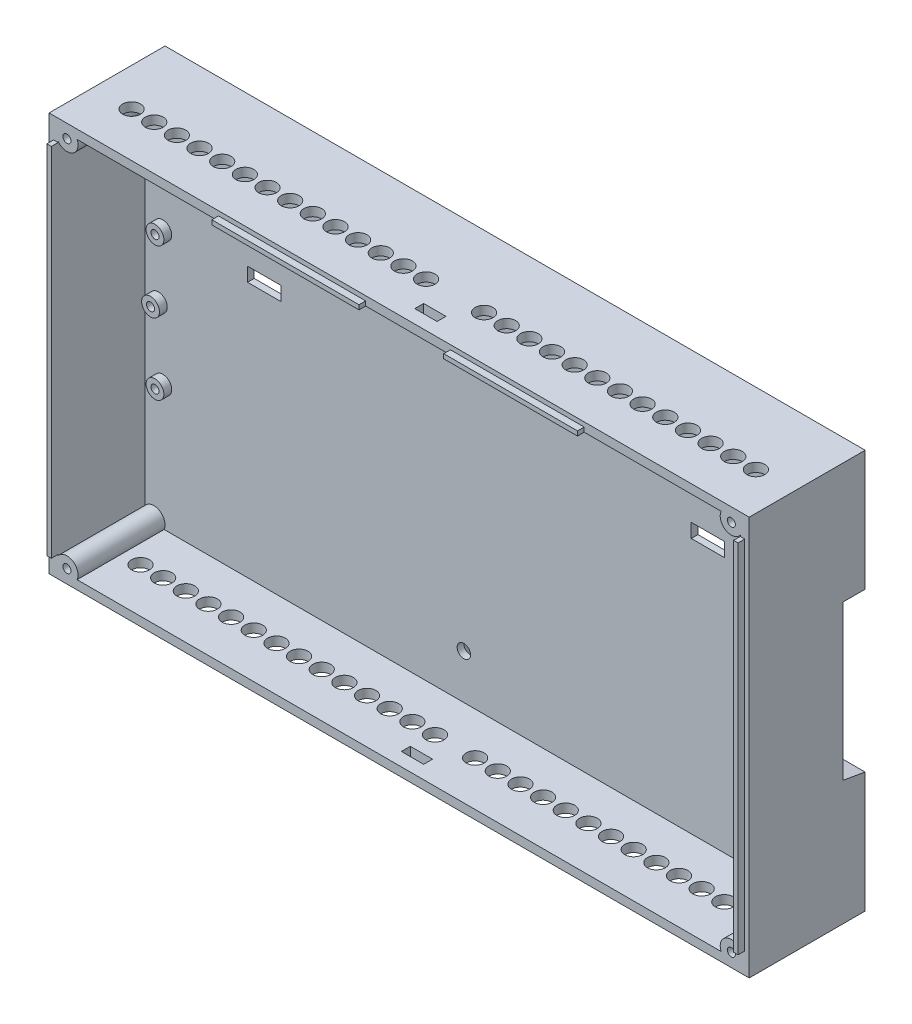
SolidWorks part; units mm, degrees
ref_plane "Front Plane" through (0, 0, 0) normal (0, 0, 1) x (1, 0, 0)
ref_plane "Top Plane" through (0, 0, 0) normal (0, 1, 0) x (1, 0, 0)
ref_plane "Right Plane" through (0, 0, 0) normal (1, 0, 0) x (0, 0, -1)
sketch "Sketch1" plane through (0, 0, 0) normal (0, 0, 1) x (1, 0, 0)
  line L1 (-78.5, 44.75) -> (78.5, 44.75)
  line L2 (-78.5, 44.75) -> (-78.5, -44.75)
  line L3 (-78.5, -44.75) -> (78.5, -44.75)
  line L4 (78.5, 44.75) -> (78.5, -44.75)
  line L5 (-78.5, 44.75) -> (78.5, -44.75) construction
  line L6 (-78.5, -44.75) -> (78.5, 44.75) construction
  point P0 (0, 0)
  dimension "D1" = 157
  dimension "D2" = 89.5
extrude "Boss-Extrude1" add sketch "Sketch1" along normal blind 26
sketch "Sketch2" plane through (0, 0, 26) normal (0, 0, 1) x (1, 0, 0)
  line L0 (78.5, 44.75) -> (-78.5, 44.75) construction
  line L1 (-76.5, 42.75) -> (76.5, 42.75)
  line L2 (-76.5, 42.75) -> (-76.5, -42.75)
  line L3 (-76.5, -42.75) -> (76.5, -42.75)
  line L4 (76.5, 42.75) -> (76.5, -42.75)
  line L5 (-76.5, 42.75) -> (76.5, -42.75) construction
  line L6 (-76.5, -42.75) -> (76.5, 42.75) construction
  line L7 (-78.5, 44.75) -> (-78.5, -44.75) construction
  point P0 (0, 0)
  dimension "D1" = 2
  dimension "D2" = 2
extrude "Cut-Extrude1" cut sketch "Sketch2" against normal blind 19.5
sketch "Sketch3" plane through (0, 0, 0) normal (0, 0, -1) x (-1, 0, 0)
  line L0 (-78.5, -44.75) -> (-78.5, 44.75) construction
  line L1 (-78.5, 17.75) -> (78.5, 17.75)
  line L2 (-78.5, 17.75) -> (-78.5, -17.75)
  line L3 (-78.5, -17.75) -> (78.5, -17.75)
  line L4 (78.5, 17.75) -> (78.5, -17.75)
  line L5 (78.5, 44.75) -> (78.5, -44.75) construction
  line L6 (78.5, -44.75) -> (-78.5, -44.75) construction
  line L7 (-78.5, 44.75) -> (78.5, 44.75) construction
  dimension "D1" = 27
  dimension "D2" = 27
extrude "Cut-Extrude2" cut sketch "Sketch3" against normal blind 5
sketch "Sketch4" plane through (0, 0, 0) normal (0, 0, -1) x (-1, 0, 0)
  line L0 (78.5, 44.75) -> (78.5, 17.75) construction
  line L1 (-76.5, 42.75) -> (76.5, 42.75)
  line L2 (-76.5, 42.75) -> (-76.5, 19.75)
  line L3 (-76.5, 19.75) -> (76.5, 19.75)
  line L4 (76.5, 42.75) -> (76.5, 19.75)
  line L5 (-76.5, 42.75) -> (76.5, 19.75) construction
  line L6 (-76.5, 19.75) -> (76.5, 42.75) construction
  line L7 (-78.5, 44.75) -> (78.5, 44.75) construction
  line L8 (78.5, 17.75) -> (-78.5, 17.75) construction
  line L9 (78.5, -17.75) -> (78.5, -44.75) construction
  line L10 (-76.5, -19.75) -> (76.5, -19.75)
  line L11 (-76.5, -19.75) -> (-76.5, -42.75)
  line L12 (-76.5, -42.75) -> (76.5, -42.75)
  line L13 (76.5, -19.75) -> (76.5, -42.75)
  line L14 (-76.5, -19.75) -> (76.5, -42.75) construction
  line L15 (-76.5, -42.75) -> (76.5, -19.75) construction
  line L16 (78.5, -44.75) -> (-78.5, -44.75) construction
  line L18 (-78.5, -17.75) -> (78.5, -17.75) construction
  point P0 (0, 31.25)
  point P12 (0, -31.25)
  dimension "D1" = 2
  dimension "D2" = 0
  dimension "D3" = 2
  dimension "D4" = 2
  dimension "D5" = 2
  dimension "D6" = 0
  dimension "D7" = 2
  dimension "D8" = 2
extrude "Cut-Extrude3" cut sketch "Sketch4" against normal blind 5
chamfer "Chamfer1" distance 5 angle 10 1 edges at (0, -17.75, 5) first distance on face at (0, -17.75, 2.5)
sketch "Sketch5" plane through (0, 0, 5) normal (0, 0, -1) x (-1, 0, 0)
  line L0 (76.5, -19.75) -> (-76.5, -19.75) construction
  line L1 (-8.75, -19.75) -> (8.75, -19.75)
  line L2 (-8.75, -19.75) -> (-8.75, -42.75)
  line L3 (-8.75, -42.75) -> (8.75, -42.75)
  line L4 (8.75, -19.75) -> (8.75, -42.75)
  line L5 (-76.5, -42.75) -> (76.5, -42.75) construction
  dimension "D1" = 17.5
  dimension "D2" = 8.75
extrude "Boss-Extrude2" add sketch "Sketch5" along normal up to surface (5 mm away) up to face at (0, -31.25, 0)
sketch "Sketch6" plane through (0, -44.75, 0) normal (0, -1, 0) x (1, 0, 0)
  line L0 (-78.5, 0) -> (78.5, 0) construction
  line L1 (7.25, 2) -> (-7.25, 2)
  line L2 (7.25, 2) -> (7.25, 5)
  line L3 (7.25, 5) -> (-7.25, 5)
  line L4 (-7.25, 2) -> (-7.25, 5)
  point P6 (0, 0)
  dimension "D1" = 14.5
  dimension "D2" = 7.25
  dimension "D3" = 2
  dimension "D4" = 5
extrude "Cut-Extrude4" cut sketch "Sketch6" against normal up to next
sketch "Sketch7" plane through (0, 0, 0) normal (0, 0, -1) x (-1, 0, 0)
  line L0 (78.5, -44.75) -> (-78.5, -44.75) construction
  line L1 (-6, -31.75) -> (6, -31.75)
  line L2 (-6, -31.75) -> (-6, -44.75)
  line L3 (-6, -44.75) -> (6, -44.75)
  line L4 (6, -31.75) -> (6, -44.75)
  line L5 (-6, -31.75) -> (6, -44.75) construction
  line L6 (-6, -44.75) -> (6, -31.75) construction
  point P0 (0, -38.25)
  dimension "D1" = 12
  dimension "D2" = 0
  dimension "D3" = 0
  dimension "D4" = 13
extrude "Cut-Extrude5" cut sketch "Sketch7" against normal up to next
chamfer "Chamfer2" distance 2 angle 21 1 edges at (6, -44.75, 1) first distance on face at (6, -38.25, 1)
chamfer "Chamfer3" distance 2 angle 21 1 edges at (-6, -44.75, 1) first distance on face at (-6, -38.25, 1)
sketch "Sketch8" plane through (0, 0, 5) normal (0, 0, -1) x (-1, 0, 0)
  line L0 (78.5, -17.75) -> (78.5, -44.75) construction
  line L1 (-7.25, -44.75) -> (7.25, -44.75) construction
  circle A0 centre (5, -32.75) radius 1.5
  dimension "D1" = 3
  dimension "D2" = 73.5
  dimension "D3" = 12
extrude "Cut-Extrude6" cut sketch "Sketch8" against normal through all
sketch "Sketch9" plane through (0, 17.75, 0) normal (0, -1, 0) x (1, 0, 0)
  line L0 (-78.5, 0) -> (78.5, 0) construction
  line L1 (53.5, 0) -> (46, 0)
  line L2 (53.5, 0) -> (53.5, 3)
  line L3 (53.5, 3) -> (46, 3)
  line L4 (46, 0) -> (46, 3)
  line L5 (78.5, 5) -> (78.5, 0) construction
  line L6 (0, -14.7612) -> (0, 18.2694) construction
  line L7 (-46, 0) -> (-46, 3)
  line L8 (-53.5, 3) -> (-46, 3)
  line L9 (-53.5, 0) -> (-53.5, 3)
  line L10 (-53.5, 0) -> (-46, 0)
  dimension "D1" = 7.5
  dimension "D2" = 32.5
  dimension "D3" = 3
extrude "Boss-Extrude3" add sketch "Sketch9" along normal blind 3
sketch "Sketch10" plane through (0, 0, 5) normal (0, 0, -1) x (-1, 0, 0)
  line L0 (78.5, 17.75) -> (-78.5, 17.75) construction
  line L1 (-53.5, 17.75) -> (-46, 17.75)
  line L2 (-53.5, 17.75) -> (-53.5, 14.6132)
  line L3 (-53.5, 14.6132) -> (-46, 14.6132)
  line L4 (-46, 17.75) -> (-46, 14.6132)
  line L5 (-78.5, 17.75) -> (-78.5, -16.8684) construction
  line L6 (0, -6.1265) -> (0, 10.5776) construction
  line L7 (46, 17.75) -> (46, 14.6132)
  line L8 (53.5, 14.6132) -> (46, 14.6132)
  line L9 (53.5, 17.75) -> (53.5, 14.6132)
  line L10 (53.5, 17.75) -> (46, 17.75)
  dimension "D1" = 7.5
  dimension "D2" = 32.5
extrude "Cut-Extrude7" cut sketch "Sketch10" against normal through all
sketch "Sketch11" plane through (0, 0, 5) normal (0, 0, -1) x (-1, 0, 0)
  line L0 (-8.75, -19.75) -> (-76.5, -19.75) construction
  line L1 (-34, -19.75) -> (-32.5, -19.75)
  line L2 (-34, -19.75) -> (-34, -23.75)
  line L3 (-34, -23.75) -> (-32.5, -23.75)
  line L4 (-32.5, -19.75) -> (-32.5, -23.75)
  line L5 (-78.5, -44.75) -> (-78.5, -17.75) construction
  line L6 (0, -7.5065) -> (0, 10.4951) construction
  line L7 (32.5, -19.75) -> (32.5, -23.75)
  line L8 (34, -23.75) -> (32.5, -23.75)
  line L9 (34, -19.75) -> (34, -23.75)
  line L10 (34, -19.75) -> (32.5, -19.75)
  circle A0 centre (-28, -22.75) radius 1
  circle A1 centre (28, -22.75) radius 1
  dimension "D1" = 2
  dimension "D2" = 1.5
  dimension "D3" = 4
  dimension "D4" = 3
  dimension "D5" = 6
  dimension "D6" = 46
extrude "Boss-Extrude4" add sketch "Sketch11" along normal blind 3
sketch "Sketch12" plane through (0, 0, 6.5) normal (0, 0, 1) x (1, 0, 0)
  line L0 (-78.5, 44.75) -> (-78.5, -44.75) construction
  line L1 (78.5, 44.75) -> (-78.5, 44.75) construction
  line L2 (17.0916, 0) -> (-18.9924, 0) construction
  line L3 (0, 18.8694) -> (0, -21.0996) construction
  circle A0 centre (-74.5, 41.75) radius 2.5
  circle A1 centre (-74.5, -41.75) radius 2.5
  circle A2 centre (74.5, -41.75) radius 2.5
  circle A3 centre (74.5, 41.75) radius 2.5
  dimension "D1" = 4
  dimension "D3" = 5
  dimension "D2" = 3
extrude "Boss-Extrude5" add sketch "Sketch12" along normal up to surface (19.5 mm away) up to face at (0, 0, 26)
sketch "Sketch13" plane through (0, 0, 26) normal (0, 0, 1) x (1, 0, 0)
  line L0 (0, 16.7956) -> (0, -13.4982) construction
  line L1 (8.3664, 0) -> (-10.8674, 0) construction
  circle A0 centre (-74.5, 41.75) radius 0.9001
  circle A1 centre (-74.5, -41.75) radius 0.9001
  circle A2 centre (74.5, -41.75) radius 0.9001
  circle A3 centre (74.5, 41.75) radius 0.9001
  dimension "D1" = 1.8002
extrude "Cut-Extrude8" cut sketch "Sketch13" against normal blind 5
sketch "Sketch14" plane through (0, 0, 26) normal (0, 0, 1) x (1, 0, 0)
  line L1 (-76.5, 40) -> (-77.5, 40)
  line L2 (-76.5, 40) -> (-76.5, -40)
  line L3 (-76.5, -40) -> (-77.5, -40)
  line L4 (-77.5, 40) -> (-77.5, -40)
  line L5 (-76.5, 40) -> (-77.5, -40) construction
  line L6 (-76.5, -40) -> (-77.5, 40) construction
  line L7 (0, -8.87) -> (0, 11.6856) construction
  line L8 (76.5, -40) -> (77.5, 40) construction
  line L9 (76.5, 40) -> (77.5, -40) construction
  line L10 (77.5, 40) -> (77.5, -40)
  line L11 (76.5, -40) -> (77.5, -40)
  line L12 (76.5, 40) -> (76.5, -40)
  line L13 (76.5, 40) -> (77.5, 40)
  line L14 (-76.5, 40.25) -> (-76.5, -40.25) construction
  point P0 (-77, 0)
  point P14 (77, 0)
  point P17 (-103.6597, 9.9725)
  dimension "D1" = 1
  dimension "D2" = 80
  dimension "D4" = 0
  dimension "D5" = 0
extrude "Boss-Extrude6" add sketch "Sketch14" along normal blind 1.5
sketch "Sketch15" plane through (0, 0, 6.5) normal (0, 0, 1) x (1, 0, 0)
  line L0 (-72.2087, -42.75) -> (72.2087, -42.75) construction
  line L1 (-76.5, 40.25) -> (-76.5, -40.25) construction
  line L2 (0, -9.1732) -> (0, 11.2988) construction
  circle A0 centre (-72.5, -14.75) radius 2
  circle A1 centre (-73.5, 0.75) radius 2
  circle A2 centre (-72.5, 15.25) radius 2
  circle A3 centre (-72.5, -14.75) radius 0.9
  circle A4 centre (-73.5, 0.75) radius 0.9
  circle A5 centre (-72.5, 15.25) radius 0.9
  circle A6 centre (72.5, 15.25) radius 0.9
  circle A7 centre (73.5, 0.75) radius 0.9
  circle A8 centre (72.5, -14.75) radius 0.9
  circle A9 centre (72.5, 15.25) radius 2
  circle A10 centre (73.5, 0.75) radius 2
  circle A11 centre (72.5, -14.75) radius 2
  dimension "D1" = 4
  dimension "D4" = 4
  dimension "D7" = 4
  dimension "D2" = 28
  dimension "D3" = 4
  dimension "D5" = 3
  dimension "D6" = 43.5
  dimension "D8" = 4
  dimension "D9" = 58
extrude "Boss-Extrude7" add sketch "Sketch15" along normal blind 1.75
sketch "Sketch16" plane through (0, -44.75, 0) normal (0, -1, 0) x (-1, 0, 0)
  line L0 (78.5, -26) -> (-78.5, -26) construction
  line L1 (2.5, -23) -> (-2.5, -23)
  line L2 (2.5, -23) -> (2.5, -21)
  line L3 (2.5, -21) -> (-2.5, -21)
  line L4 (-2.5, -23) -> (-2.5, -21)
  line L5 (2.5, -23) -> (-2.5, -21) construction
  line L6 (2.5, -21) -> (-2.5, -23) construction
  point P0 (0, -22)
  dimension "D1" = 5
  dimension "D2" = 0
  dimension "D3" = 2
  dimension "D4" = 4
extrude "Cut-Extrude9" cut sketch "Sketch16" against normal up to next
sketch "Sketch17" plane through (0, 44.75, 0) normal (0, 1, 0) x (1, 0, 0)
  line L0 (-78.5, -26) -> (-78.5, 0) construction
  line L1 (5.5, -23) -> (0.5, -23)
  line L2 (5.5, -23) -> (5.5, -21)
  line L3 (5.5, -21) -> (0.5, -21)
  line L4 (0.5, -23) -> (0.5, -21)
  line L5 (5.5, -23) -> (0.5, -21) construction
  line L6 (5.5, -21) -> (0.5, -23) construction
  line L7 (78.5, -26) -> (-78.5, -26) construction
  point P0 (3, -22)
  dimension "D1" = 2
  dimension "D2" = 5
  dimension "D3" = 81.5
  dimension "D4" = 4
extrude "Cut-Extrude10" cut sketch "Sketch17" against normal up to next
sketch "Sketch18" plane through (0, 0, 26) normal (0, 0, 1) x (1, 0, 0)
  line L1 (11.5, 43.75) -> (41.5, 43.75)
  line L2 (11.5, 43.75) -> (11.5, 42.75)
  line L3 (11.5, 42.75) -> (41.5, 42.75)
  line L4 (41.5, 43.75) -> (41.5, 42.75)
  line L5 (78.5, -44.75) -> (78.5, 44.75) construction
  line L6 (-77.5, 40) -> (-77.5, -40) construction
  line L7 (-78.5, 44.75) -> (-78.5, -44.75) construction
  line L8 (-7.5, 43.75) -> (-40.5, 43.75)
  line L9 (-7.5, 43.75) -> (-7.5, 42.75)
  line L10 (-7.5, 42.75) -> (-40.5, 42.75)
  line L11 (-40.5, 43.75) -> (-40.5, 42.75)
  line L12 (72.2087, 42.75) -> (-72.2087, 42.75) construction
  dimension "D1" = 1
  dimension "D2" = 67
  dimension "D3" = 119
  dimension "D4" = 1
  dimension "D5" = 71
  dimension "D6" = 119
  dimension "D7" = 0
  dimension "D8" = 0
extrude "Boss-Extrude8" add sketch "Sketch18" along normal blind 1.5
sketch "Sketch19" plane through (0, -44.75, 0) normal (0, -1, 0) x (1, 0, 0)
  line L0 (-78.5, 26) -> (-78.5, 0) construction
  line L1 (-78.5, 26) -> (78.5, 26) construction
  line L2 (78.5, 26) -> (78.5, 0) construction
  circle A0 centre (-68, 16) radius 2
  circle A1 centre (-62.92, 16) radius 2
  circle A2 centre (-57.84, 16) radius 2
  circle A3 centre (-52.76, 16) radius 2
  circle A4 centre (-47.68, 16) radius 2
  circle A5 centre (-42.6, 16) radius 2
  circle A6 centre (-37.52, 16) radius 2
  circle A7 centre (-32.44, 16) radius 2
  circle A8 centre (-27.36, 16) radius 2
  circle A9 centre (-22.28, 16) radius 2
  circle A10 centre (-17.2, 16) radius 2
  circle A11 centre (-12.12, 16) radius 2
  circle A12 centre (-7.04, 16) radius 2
  circle A13 centre (-1.96, 16) radius 2
  circle A14 centre (68, 16) radius 2
  circle A15 centre (62.92, 16) radius 2
  circle A16 centre (57.84, 16) radius 2
  circle A17 centre (52.76, 16) radius 2
  circle A18 centre (47.68, 16) radius 2
  circle A19 centre (42.6, 16) radius 2
  circle A20 centre (37.52, 16) radius 2
  circle A21 centre (32.44, 16) radius 2
  circle A22 centre (27.36, 16) radius 2
  circle A23 centre (22.28, 16) radius 2
  circle A24 centre (17.2, 16) radius 2
  circle A25 centre (12.12, 16) radius 2
  circle A26 centre (7.04, 16) radius 2
  dimension "D1" = 10.5
  dimension "D2" = 4
  dimension "D5" = 4
  dimension "D3" = 10
  dimension "D6" = 10
  dimension "D7" = 10.5
  dimension "D4" = 14
  dimension "D8" = 13
extrude "Cut-Extrude11" cut sketch "Sketch19" against normal up to next (2 mm away)
sketch "Sketch20" plane through (0, 44.75, 0) normal (0, 1, 0) x (1, 0, 0)
  line L0 (73.6094, -16) -> (-67.7386, -16) construction
  line L1 (78.5, -26) -> (-78.5, -26) construction
  line L2 (-78.5, -26) -> (-78.5, 0) construction
  line L3 (78.5, -26) -> (78.5, 0) construction
  circle A0 centre (-70, -16) radius 2
  circle A1 centre (-64.92, -16) radius 2
  circle A2 centre (-59.84, -16) radius 2
  circle A3 centre (-54.76, -16) radius 2
  circle A4 centre (-49.68, -16) radius 2
  circle A5 centre (-44.6, -16) radius 2
  circle A6 centre (-39.52, -16) radius 2
  circle A7 centre (-34.44, -16) radius 2
  circle A8 centre (-29.36, -16) radius 2
  circle A9 centre (-24.28, -16) radius 2
  circle A10 centre (-19.2, -16) radius 2
  circle A11 centre (-14.12, -16) radius 2
  circle A12 centre (-9.04, -16) radius 2
  circle A13 centre (-3.96, -16) radius 2
  circle A14 centre (70, -16) radius 2
  circle A15 centre (64.92, -16) radius 2
  circle A16 centre (59.84, -16) radius 2
  circle A17 centre (54.76, -16) radius 2
  circle A18 centre (49.68, -16) radius 2
  circle A19 centre (44.6, -16) radius 2
  circle A20 centre (39.52, -16) radius 2
  circle A21 centre (34.44, -16) radius 2
  circle A22 centre (29.36, -16) radius 2
  circle A23 centre (24.28, -16) radius 2
  circle A24 centre (19.2, -16) radius 2
  circle A25 centre (14.12, -16) radius 2
  circle A26 centre (9.04, -16) radius 2
  dimension "D2" = 4
  dimension "D5" = 8.5
  dimension "D6" = 4
  dimension "D1" = 10
  dimension "D3" = 8.5
  dimension "D4" = 14
  dimension "D7" = 13
extrude "Cut-Extrude12" cut sketch "Sketch20" against normal up to next (2 mm away)
